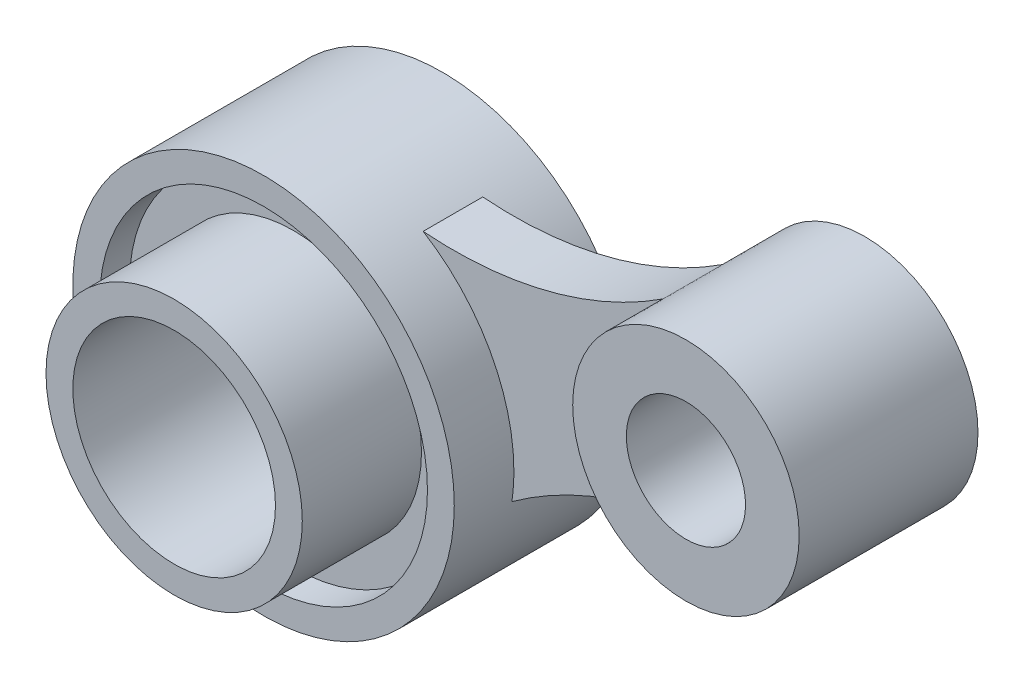
SolidWorks part; units mm, degrees
material "1060 Alloy"
ref_plane "Plan de face" through (0, 0, 0) normal (0, 0, 1) x (1, 0, 0)
ref_plane "Plan de dessus" through (0, 0, 0) normal (0, 1, 0) x (1, 0, 0)
ref_plane "Plan de droite" through (0, 0, 0) normal (1, 0, 0) x (0, 0, -1)
sketch "Sketch1" plane through (0, 0, 0) normal (0, 0, 1) x (1, 0, 0)
  circle A0 centre (-34.339, -15.6195) radius 32
  circle A1 centre (-34.339, -15.6195) radius 27.5
  circle A2 centre (-34.339, -15.6195) radius 21.5
  circle A3 centre (-34.339, -15.6195) radius 17
  circle A4 centre (36.5279, 8.9343) radius 19
  circle A5 centre (36.5279, 8.9343) radius 10
  arc A6 (-17.5609, 11.6293) -> (22.6481, 21.9093) centre (-12.4527, 75.4251) ccw
  arc A7 (-2.6675, -20.193) -> (28.5172, -8.2945) centre (34.9504, -71.9703) cw
  dimension "D1" = 64
  dimension "D2" = 55
  dimension "D3" = 43
  dimension "D4" = 34
  dimension "D5" = 38
  dimension "D6" = 20
  dimension "D8" = 64
  dimension "D9" = 64
  dimension "D7" = 75
extrude "Boss-Extrude1" add sketch "Sketch1" along normal mid plane 30 contours A0 | A4
extrude "Boss-Extrude2" add sketch "Sketch1<3>" along normal mid plane 10 contours A0 A7 A4 A6 region at (6.5022, 0.8088, 0)
sketch "Sketch1<3>" plane through (0, 0, 0) normal (0, 0, 1) x (1, 0, 0) same geometry as "Sketch1"
extrude "Cut-Extrude1" cut sketch "Sketch1<4>" against normal through all both and the other way through all contours A3 | A5
sketch "Sketch1<4>" plane through (0, 0, 0) normal (0, 0, 1) x (1, 0, 0) same geometry as "Sketch1"
extrude "Boss-Extrude3" add sketch "Sketch1<5>" along normal blind 15 from surface contours A2 | A3 starting at face at (-17.339, -15.6195, 15)
sketch "Sketch1<5>" plane through (0, 0, 0) normal (0, 0, 1) x (1, 0, 0) same geometry as "Sketch1"
extrude "Cut-Extrude2" cut sketch "Sketch1<6>" against normal blind 5 and the other way through all from surface contours A1 | A2 starting at face at (-2.339, -15.6195, 15)
sketch "Sketch1<6>" plane through (0, 0, 0) normal (0, 0, 1) x (1, 0, 0) same geometry as "Sketch1"
